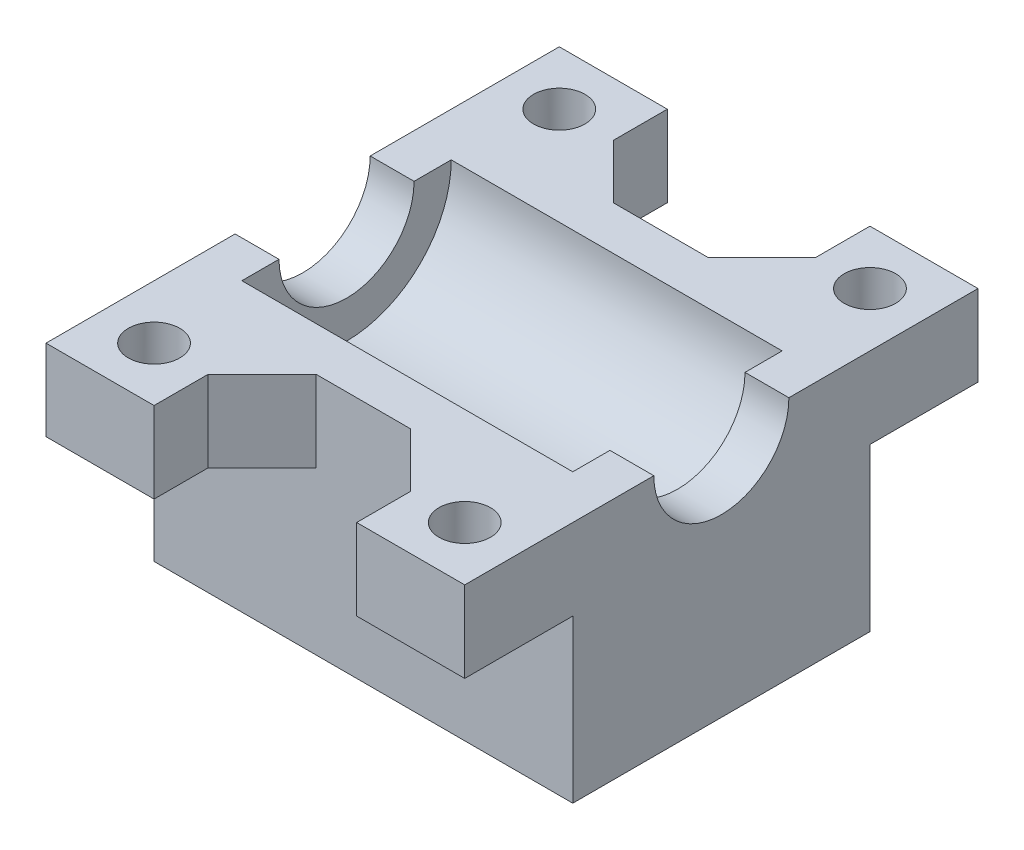
SolidWorks part; units mm, degrees
ref_plane "Front Plane" through (0, 0, 0) normal (0, 0, 1) x (1, 0, 0)
ref_plane "Top Plane" through (0, 0, 0) normal (0, 1, 0) x (1, 0, 0)
ref_plane "Right Plane" through (0, 0, 0) normal (1, 0, 0) x (0, 0, -1)
sketch "Sketch1" plane through (0, 0, 0) normal (0, 1, 0) x (1, 0, 0)
  line L1 (-15.5, 11) -> (15.5, 11)
  line L2 (-15.5, 11) -> (-15.5, -11)
  line L3 (-15.5, -11) -> (15.5, -11)
  line L4 (15.5, 11) -> (15.5, -11)
  line L5 (-15.5, 11) -> (15.5, -11) construction
  line L6 (-15.5, -11) -> (15.5, 11) construction
  point P0 (0, 0)
  dimension "D1" = 31
  dimension "D2" = 22
extrude "Boss-Extrude1" add sketch "Sketch1" along normal blind 11
sketch "Sketch2" plane through (0, 0, 0) normal (0, 1, 0) x (1, 0, 0)
  line L4 (15.5, -11) -> (15.5, 11)
  line L5 (-15.5, -11) -> (15.5, -11)
  line L6 (-15.5, 11) -> (-15.5, -11)
  line L7 (15.5, 11) -> (-15.5, 11)
  line L8 (15.5, -11) -> (15.5, 11)
  line L9 (-15.5, -11) -> (15.5, -11)
  line L10 (-15.5, 11) -> (-15.5, -11)
  line L11 (15.5, 11) -> (-15.5, 11)
  circle A0 centre (0, 0) radius 4
  dimension "D2" = 8
  dimension "D1" = 0
extrude "Boss-Extrude2" add sketch "Sketch2" against normal blind 7
sketch "Sketch3" plane through (0, 11, 0) normal (0, 1, 0) x (1, 0, 0)
  line L1 (12.25, -7.75) -> (-12.25, -7.75)
  line L2 (12.25, -7.75) -> (12.25, 7.75)
  line L3 (12.25, 7.75) -> (-12.25, 7.75)
  line L4 (-12.25, -7.75) -> (-12.25, 7.75)
  line L5 (12.25, -7.75) -> (-12.25, 7.75) construction
  line L6 (12.25, 7.75) -> (-12.25, -7.75) construction
  point P0 (0, 0)
  dimension "D1" = 15.5
  dimension "D2" = 24.5
extrude "Cut-Extrude1" cut sketch "Sketch3" against normal blind 7.75
fillet "Fillet1" radius 7.75 2 edges at (0, 3.25, 7.75) (0, 3.25, -7.75)
sketch "Sketch4" plane through (-12.25, 0, 0) normal (1, 0, 0) x (0, 0, -1)
  line L0 (7.75, 11) -> (-7.75, 11) construction
  circle A0 centre (0, 11) radius 5
  dimension "D1" = 10
extrude "Cut-Extrude2" cut sketch "Sketch4" against normal through all both and the other way through all
sketch "Sketch5" plane through (0, 11, 0) normal (0, 1, 0) x (1, 0, 0)
  line L1 (15.5, -11) -> (7.5, -11)
  line L2 (15.5, -11) -> (15.5, -19)
  line L3 (15.5, -19) -> (7.5, -19)
  line L4 (7.5, -11) -> (7.5, -19)
  circle A0 centre (11.5, -15) radius 1.9058
  dimension "D1" = 8
  dimension "D2" = 8
  dimension "D3" = 4
  dimension "D4" = 4
extrude "Boss-Extrude3" add sketch "Sketch5" against normal blind 6
sketch "Sketch6" plane through (0, 5, 0) normal (0, -1, 0) x (1, 0, 0)
  line L4 (15.5, 11) -> (15.5, 19)
  line L5 (15.5, 19) -> (7.5, 19)
  line L6 (7.5, 19) -> (7.5, 11)
  line L7 (7.5, 11) -> (15.5, 11)
  line L8 (15.5, 11) -> (15.5, 19)
  line L9 (15.5, 19) -> (7.5, 19)
  line L10 (7.5, 19) -> (7.5, 11)
  line L11 (7.5, 11) -> (15.5, 11)
  circle A0 centre (11.5, 15) radius 1.9058 construction
  circle A1 centre (11.5, 15) radius 1.9058
  circle A2 centre (11.5, 15) radius 3
  circle M6 centre (11.5, 15) radius 1.9058
  dimension "D2" = 6
  dimension "D1" = 0
extrude "Cut-Extrude3" cut sketch "Sketch6" against normal blind 3 contours A2 M6 region at (8.5849, 5, 15)
mirror "Mirror8" about plane through (0, 0, 0) normal (1, 0, 0) of "Cut-Extrude3", "Boss-Extrude3"
mirror "Mirror9" about plane through (0, 0, 0) normal (0, 0, 1) of "Mirror8"
chamfer "Chamfer2" distance 4 angle 45 4 edges at (-7.5, 8, 11) (7.5, 8, 11) (-7.5, 8, -11) (7.5, 8, -11)
sketch "Sketch7" plane through (0, 0, 0) normal (0, -1, 0) x (1, 0, 0)
  circle A1 centre (0, 0) radius 4
  circle A2 centre (0, 0) radius 4
  dimension "D1" = 0
extrude "Boss-Extrude4" add sketch "Sketch7" along normal blind 1
